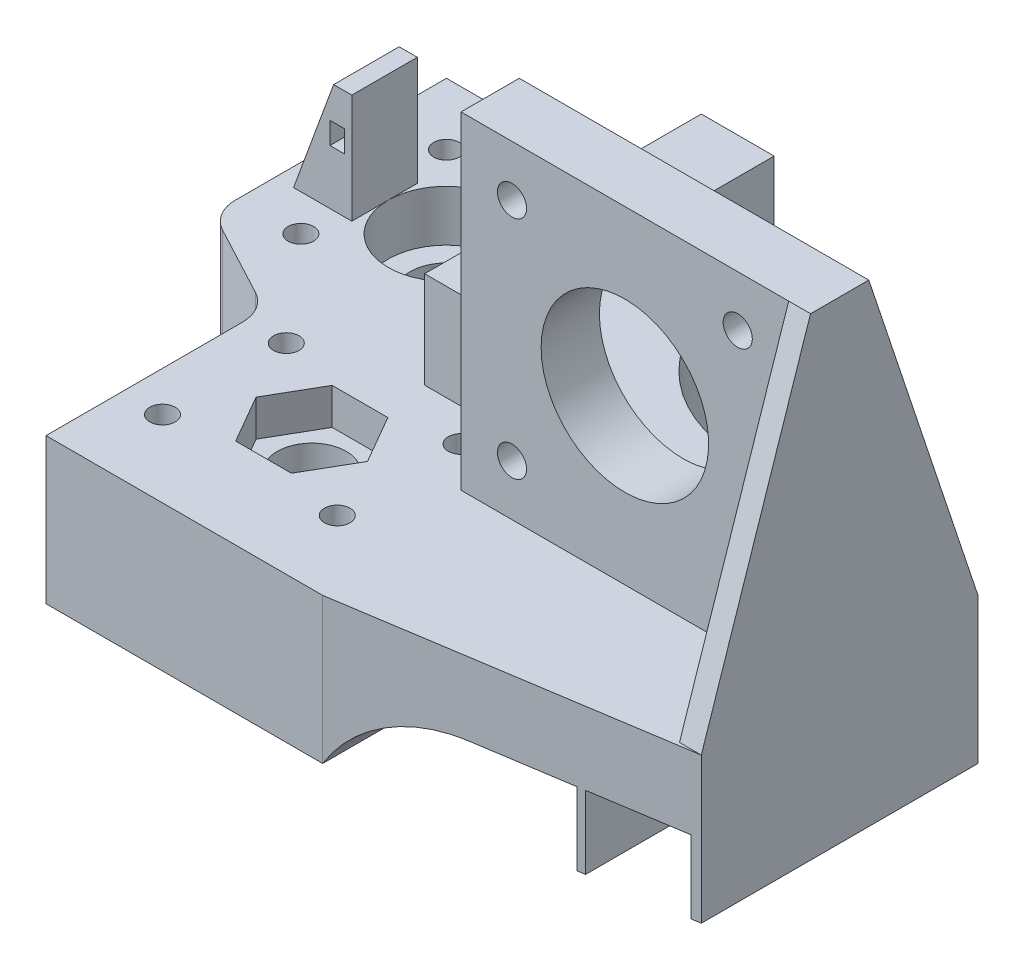
SolidWorks part; units mm, degrees
material "ABS PC"
ref_plane "Front Plane" through (0, 0, 0) normal (0, 0, 1) x (1, 0, 0)
ref_plane "Top Plane" through (0, 0, 0) normal (0, 1, 0) x (1, 0, 0)
ref_plane "Right Plane" through (0, 0, 0) normal (1, 0, 0) x (0, 0, -1)
sketch "Sketch1" plane through (0, 0, 0) normal (0, 1, 0) x (1, 0, 0)
  line L0 (0, 0) -> (0, 70)
  line L1 (0, 0) -> (98, 0)
  line L2 (0, 70) -> (98, 70)
  line L3 (98, 0) -> (98, 70)
  dimension "D1" = 70
  dimension "D2" = 98
extrude "Boss-Extrude1" add sketch "Sketch1" along normal blind 10
sketch "Sketch22" plane through (0, 0, 0) normal (0, -1, 0) x (1, 0, 0)
  line L0 (53, 0) -> (53, -70)
  line L1 (53, -70) -> (0, -70)
  line L2 (0, -70) -> (0, -38)
  line L3 (0, -38) -> (15, -30)
  line L8 (15, 0) -> (53, 0)
  line L9 (15, 0) -> (15, -30)
  dimension "D1" = 53
  dimension "D2" = 38
  dimension "D3" = 70
  dimension "D4" = 30
  dimension "D5" = 32
extrude "Boss-Extrude5" add sketch "Sketch22" along normal blind 10
sketch "Sketch2" plane through (0, 10, 0) normal (0, 1, 0) x (-1, 0, 0)
  line L0 (-98, -70) -> (0, -70) construction
  line L1 (0, -70) -> (0, 0) construction
  circle A0 centre (-18.5, -51.5) radius 5
  circle A1 centre (-32.5, -19) radius 4.75
  dimension "D1" = 10
  dimension "D2" = 9.5
  dimension "D3" = 14
  dimension "D4" = 32.5
  dimension "D5" = 18.5
  dimension "D6" = 18.5
extrude "Cut-Extrude1" cut sketch "Sketch2" against normal through all
sketch "Sketch3" plane through (0, 10, 0) normal (0, 1, 0) x (1, 0, 0)
  line L1 (36.325, 25.6251) -> (28.675, 25.6251)
  line L2 (28.675, 25.6251) -> (24.85, 19)
  line L3 (24.85, 19) -> (28.675, 12.3749)
  line L4 (28.675, 12.3749) -> (36.325, 12.3749)
  line L5 (36.325, 12.3749) -> (40.15, 19)
  line L6 (40.15, 19) -> (36.325, 25.6251)
  circle A0 centre (32.5, 19) radius 6.6251 construction
  dimension "D1" = 15.3
extrude "Cut-Extrude2" cut sketch "Sketch3" against normal blind 5
sketch "Sketch5" plane through (0, 10, 0) normal (0, 1, 0) x (1, 0, 0)
  circle A0 centre (8.5, 61.5) radius 1.75
  circle A1 centre (28.5, 41.5) radius 1.75
  circle A2 centre (8.5, 41.5) radius 1.75
  circle A3 centre (28.5, 61.5) radius 1.75
  circle A4 centre (18.5, 51.5) radius 5 construction
  circle A6 centre (20.5, 27.5) radius 1.75
  circle A7 centre (44.5, 27.5) radius 1.75
  circle A8 centre (44.5, 10.5) radius 1.75
  circle A9 centre (20.5, 10.5) radius 1.75
  circle A10 centre (32.5, 19) radius 4 construction
  circle A11 centre (32.5, 19) radius 4 construction
  circle A12 centre (32.5, 19) radius 4.75 construction
  dimension "D1" = 3.5
  dimension "D2" = 10
  dimension "D3" = 20
  dimension "D4" = 20
  dimension "D5" = 20
  dimension "D7" = 12
  dimension "D9" = 8.5
  dimension "D10" = 10
  dimension "D6" = 12
  dimension "D8" = 8.5
extrude "Cut-Extrude3" cut sketch "Sketch5" against normal through all
sketch "Sketch7" plane through (0, 10, 0) normal (0, 1, 0) x (1, 0, 0)
  line L0 (0, 38) -> (15, 30)
  line L1 (0, 70) -> (0, 0) construction
  line L2 (15, 30) -> (15, 0)
  line L3 (0, 0) -> (98, 0) construction
  line L4 (15, 0) -> (0, 0)
  line L5 (0, 0) -> (0, 38)
  dimension "D1" = 15
  dimension "D2" = 38
  dimension "D3" = 30
extrude "Cut-Extrude5" cut sketch "Sketch7" against normal through all
sketch "Sketch26" plane through (0, -10, 0) normal (0, -1, 0) x (1, 0, 0)
  circle A0 centre (18.5, -51.5) radius 8
  dimension "D1" = 16
extrude "Cut-Extrude14" cut sketch "Sketch26" against normal blind 7
sketch "Sketch8" plane through (0, 10, 0) normal (0, 1, 0) x (1, 0, 0)
  line L0 (35, 70) -> (45, 70)
  line L1 (35, 70) -> (35, 56)
  line L2 (45, 70) -> (45, 56)
  line L3 (35, 56) -> (45, 56)
  line L4 (98, 70) -> (0, 70) construction
  line L5 (0, 70) -> (0, 38) construction
  line L6 (45, 46) -> (35, 46)
  line L7 (45, 46) -> (45, 32)
  line L8 (35, 46) -> (35, 32)
  line L9 (45, 32) -> (35, 32)
  dimension "D1" = 14
  dimension "D2" = 10
  dimension "D3" = 35
  dimension "D4" = 14
  dimension "D5" = 10
extrude "Boss-Extrude2" add sketch "Sketch8" along normal blind 13.25
sketch "Sketch9" plane through (45, 0, 0) normal (1, 0, 0) x (0, 0, -1)
  line L0 (56, 23.25) -> (56, 10) construction
  line L1 (46, 23.25) -> (46, 10) construction
  line L5 (56, 10) -> (70, 10) construction
  circle A0 centre (63, 16) radius 4.25
  circle A1 centre (39, 16) radius 4.25
  dimension "D7" = 6
  dimension "D1" = 8.5
  dimension "D3" = 7
  dimension "D2" = 7
extrude "Cut-Extrude6" cut sketch "Sketch9" against normal through all
sketch "Sketch13" plane through (0, 0, -70) normal (0, 0, -1) x (-1, 0, 0)
  line L0 (-44.2, 7) -> (-35.8, 7)
  line L1 (-44.2, 7) -> (-44.2, 1.8)
  line L2 (-35.8, 7) -> (-35.8, 1.8)
  line L3 (-44.2, 1.8) -> (-35.8, 1.8)
  line L4 (-98, 10) -> (-45, 10) construction
  line L8 (0, 10) -> (0, -10) construction
  dimension "D1" = 8.4
  dimension "D2" = 5.2
  dimension "D3" = 3
  dimension "D4" = 35.8
extrude "Cut-Extrude10" cut sketch "Sketch13" against normal blind 38
sketch "Sketch16" plane through (0, 10, 0) normal (0, 1, 0) x (-1, 0, 0)
  line L0 (-50, -30) -> (-50, -22)
  line L1 (-50, -30) -> (-95, -30)
  line L2 (-50, -22) -> (-95, -22)
  line L3 (-95, -30) -> (-95, -22)
  line L4 (-98, -70) -> (-45, -70) construction
  line L6 (-45, -56) -> (-45, -70) construction
  dimension "D1" = 8
  dimension "D2" = 40
  dimension "D3" = 5
  dimension "D4" = 45
extrude "Boss-Extrude3" add sketch "Sketch16" along normal blind 45
sketch "Sketch17" plane through (0, 0, -30) normal (0, 0, -1) x (-1, 0, 0)
  line L0 (-95, 55) -> (-95, 10) construction
  line L1 (-95, 55) -> (-50, 55) construction
  circle A0 centre (-72.5, 32.5) radius 11.5
  circle A1 centre (-88, 48) radius 2
  circle A2 centre (-57, 48) radius 2
  circle A3 centre (-57, 17) radius 2
  circle A4 centre (-88, 17) radius 2
  dimension "D1" = 23
  dimension "D3" = 22.5
  dimension "D4" = 15.5
  dimension "D5" = 15.5
  dimension "D6" = 4
  dimension "D7" = 15.5
  dimension "D8" = 15.5
  dimension "D2" = 22.5
extrude "Cut-Extrude11" cut sketch "Sketch17" against normal through all
sketch "Sketch18" plane through (95, 0, 0) normal (1, 0, 0) x (0, 0, -1)
  line L0 (22, 55) -> (7, 10)
  line L1 (7, 10) -> (22, 10)
  line L2 (22, 10) -> (30, 10)
  line L3 (30, 10) -> (45, 10)
  line L4 (45, 10) -> (30, 55)
  line L5 (30, 55) -> (22, 55)
  dimension "D1" = 15
  dimension "D2" = 15
extrude "Boss-Extrude4" add sketch "Sketch18" along normal blind 3
sketch "Sketch20" plane through (0, 10, 0) normal (0, 1, 0) x (1, 0, 0)
  line L0 (98, 7) -> (53, 0)
  line L1 (15, 0) -> (98, 0) construction
  line L2 (53, 0) -> (98, 0)
  line L3 (98, 0) -> (98, 7)
  dimension "D1" = 45
extrude "Cut-Extrude12" cut sketch "Sketch20" against normal through all
sketch "Sketch21" plane through (0, 10, 0) normal (0, 1, 0) x (1, 0, 0)
  line L0 (95, 45) -> (65.6155, 45)
  line L2 (98, 70) -> (45, 70) construction
  line L3 (45, 70) -> (98, 70)
  line L4 (98, 70) -> (98, 45)
  line L5 (98, 45) -> (95, 45)
  arc A0 (65.6155, 45) -> (45, 70) centre (65.6155, 66) cw
  dimension "D1" = 21
extrude "Cut-Extrude13" cut sketch "Sketch21" against normal through all
fillet "Fillet5" radius 5 2 edges at (15, 0, -30)
hole_wizard "Ø5.5 (5.5) Diameter Hole3" positions "Sketch24" profile "Sketch23" hole size "Ø5.5" standard "Ansi Metric"
sketch "Sketch24" plane through (0, -10, 0) normal (0, -1, 0) x (1, 0, 0)
  line L0 (0, -41) -> (0, -70) construction
  line L2 (0, -70) -> (45, -70) construction
  point P0 (40, -63)
  point P1 (40, -39)
  dimension "D1" = 40
  dimension "D2" = 7
  dimension "D3" = 24
sketch "Sketch23" plane through (40, -10, -63) normal (1, 0, 0) x (0, 0, -1)
  line L0 (0, 0) -> (0, 24.6524)
  line L1 (0, 24.6524) -> (2.75, 23)
  line L2 (2.75, 23) -> (2.75, 0)
  line L5 (2.75, 0) -> (0, 0)
  line L10 (0, 24.6524) -> (-2.75, 23) construction
  line L11 (0, -6.35) -> (0, 107.95) construction
  dimension "Hole Dia." = 5.5
  dimension "Hole Depth" = 23
  dimension "Drill Angle" = 118
fillet "Fillet8" radius 20 1 edges
sketch "Sketch27" plane through (0, 10, 0) normal (0, 1, 0) x (1, 0, 0)
  circle A0 centre (18.5, 51.5) radius 8
  dimension "D1" = 16
extrude "Cut-Extrude15" cut sketch "Sketch27" against normal blind 7
sketch "Sketch29" plane through (0, -10, 0) normal (0, -1, 0) x (1, 0, 0)
  line L1 (36.325, -12.3749) -> (28.675, -12.3749)
  line L2 (28.675, -12.3749) -> (24.85, -19)
  line L3 (24.85, -19) -> (28.675, -25.6251)
  line L4 (28.675, -25.6251) -> (36.325, -25.6251)
  line L5 (36.325, -25.6251) -> (40.15, -19)
  line L6 (40.15, -19) -> (36.325, -12.3749)
  circle A0 centre (32.5, -19) radius 6.6251 construction
  dimension "D1" = 15.3
extrude "Cut-Extrude16" cut sketch "Sketch29" against normal blind 5
sketch "Sketch30" plane through (0, 10, 0) normal (0, 1, 0) x (1, 0, 0)
  line L0 (34.5, 46.5) -> (26.5, 46.5)
  line L1 (34.5, 46.5) -> (34.5, 55.5)
  line L2 (26.5, 46.5) -> (26.5, 55.5)
  line L3 (34.5, 55.5) -> (26.5, 55.5)
  line L4 (10.5, 46.5) -> (2.5, 46.5)
  line L5 (10.5, 46.5) -> (10.5, 55.5)
  line L6 (2.5, 46.5) -> (2.5, 55.5)
  line L7 (10.5, 55.5) -> (2.5, 55.5)
  line L8 (0, 70) -> (0, 41) construction
  line L9 (35, 70) -> (0, 70) construction
  dimension "D1" = 10.5
  dimension "D2" = 26.5
  dimension "D3" = 8
  dimension "D4" = 9
  dimension "D5" = 14.5
extrude "Boss-Extrude6" add sketch "Sketch30" along normal blind 15
sketch "Sketch31" plane through (0, 0, -55.5) normal (0, 0, -1) x (-1, 0, 0)
  line L0 (-34.5, 10) -> (-34.5, 25)
  line L1 (-10.5, 25) -> (-2.5, 25) construction
  line L2 (-8, 25) -> (-2.5, 10)
  line L3 (-34.5, 25) -> (-29, 25)
  line L6 (-8, 25) -> (-2.5, 25)
  line L7 (-2.5, 25) -> (-2.5, 10)
  line L10 (-34.5, 10) -> (-29, 25)
  dimension "D1" = 5.5
extrude "Cut-Extrude17" cut sketch "Sketch31" against normal blind 9
sketch "Sketch32" plane through (0, 0, -55.5) normal (0, 0, -1) x (-1, 0, 0)
  line L0 (-27.5, 20.5) -> (-27.5, 17.5)
  line L1 (-27.5, 20.5) -> (-29.5, 20.5)
  line L2 (-27.5, 17.5) -> (-29.5, 17.5)
  line L3 (-29.5, 20.5) -> (-29.5, 17.5)
  line L4 (-26.5, 25) -> (-26.5, 10) construction
  line L5 (-29, 25) -> (-26.5, 25) construction
  line L6 (-9.5, 17.5) -> (-9.5, 20.5)
  line L7 (-9.5, 17.5) -> (-7.5, 17.5)
  line L8 (-9.5, 20.5) -> (-7.5, 20.5)
  line L9 (-7.5, 17.5) -> (-7.5, 20.5)
  line L10 (-10.5, 25) -> (-10.5, 10) construction
  dimension "D1" = 2
  dimension "D2" = 3
  dimension "D3" = 1
  dimension "D4" = 4.5
  dimension "D5" = 1
extrude "Cut-Extrude18" cut sketch "Sketch32" against normal blind 9
sketch "Sketch25" plane through (0, 0, 0) normal (0, -1, 0) x (1, 0, 0)
  line L0 (98, -45) -> (98, -7)
  line L1 (98, -7) -> (96.75, -6.8056)
  line L2 (98, -7) -> (70.3205, -2.6943) construction
  line L3 (96.75, -6.8056) -> (96.75, -45)
  line L4 (70.3205, -45) -> (98, -45) construction
  line L5 (96.75, -45) -> (98, -45)
  line L6 (84.25, -45) -> (84.25, -4.8611)
  line L7 (84.25, -4.8611) -> (83.25, -4.7056)
  line L8 (83.25, -4.7056) -> (83.25, -45)
  line L9 (83.25, -45) -> (84.25, -45)
  dimension "D1" = 1.25
  dimension "D2" = 1
  dimension "D3" = 12.5
extrude "bridge build help" add sketch "Sketch25" along normal blind 10
